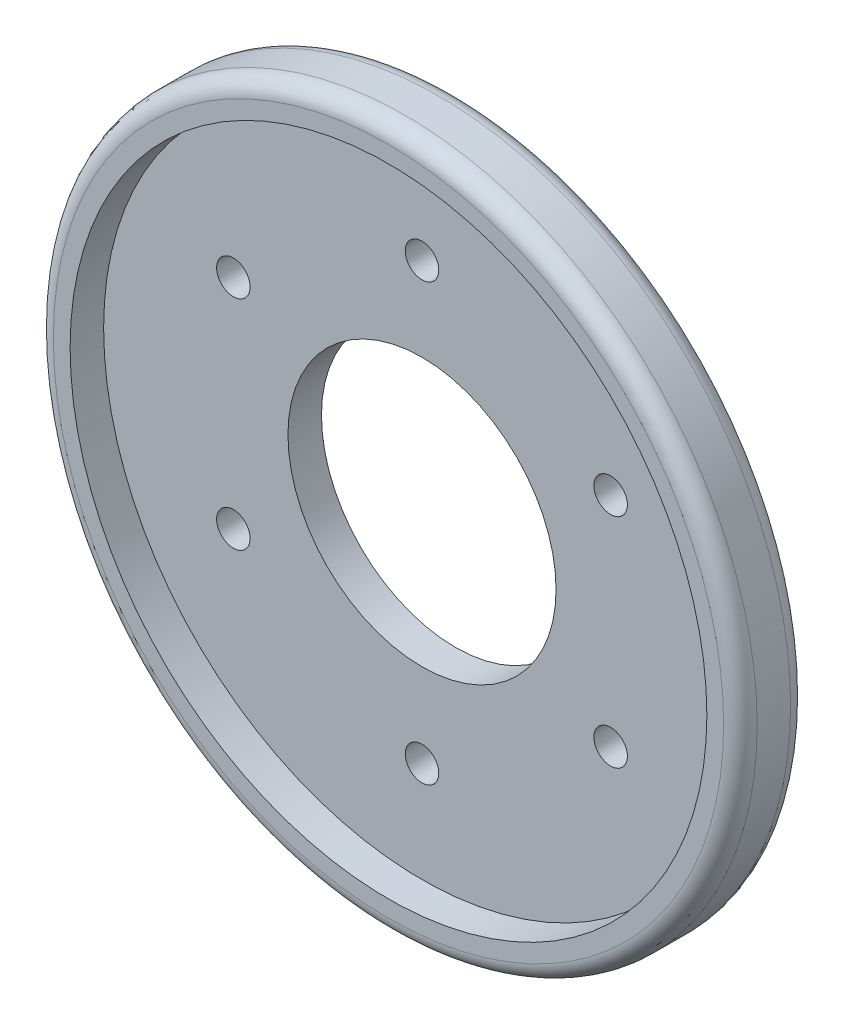
SolidWorks part; units mm, degrees
note: The reader was unsure of these and kept them because the rebuilt part matched: shared geometry of "Эскиз1<5>".
ref_plane "Спереди" through (0, 0, 0) normal (0, 0, 1) x (1, 0, 0)
ref_plane "Сверху" through (0, 0, 0) normal (0, 1, 0) x (1, 0, 0)
ref_plane "Справа" through (0, 0, 0) normal (1, 0, 0) x (0, 0, -1)
other "Configuration Table"
sketch "Эскиз1" plane through (0, 0, 0) normal (0, 0, 1) x (1, 0, 0)
  line L7 (0, 19) -> (0, 21)
  line L8 (0, -21) -> (0, -19)
  circle A0 centre (0, 0) radius 19
  circle A2 centre (0, 0) radius 8
  circle A11 centre (0, 0) radius 21
  point P11 (39.3976, -24.5909)
  dimension "D1" = 38
  dimension "D3" = 16
  dimension "D5" = 21
extrude "Бобышка-Вытянуть1" add sketch "Эскиз1" along normal blind 2
extrude "Бобышка-Вытянуть3" add sketch "Эскиз1<5>" along normal blind 4 contours L7 A11 L8 A0 | L8 A11 L7 A0
sketch "Эскиз1<5>" plane through (0, 0, 0) normal (0, 0, 1) x (1, 0, 0) same geometry as "Эскиз1"
fillet "Скругление1" radius 1 2 edges at (21, 0, 0) (21, 0, 4)
sketch "Эскиз3" plane through (0, 0, 2) normal (0, 0, 1) x (1, 0, 0)
  line L0 (0, 0) -> (0, 12.9985) construction
  line L1 (-11.2571, 6.4993) -> (0, 0) construction
  line L2 (0, 0) -> (11.2571, 6.4993) construction
  circle A6 centre (11.2571, 6.4993) radius 1
  circle A7 centre (11.2571, -6.4993) radius 1
  circle A8 centre (0, -12.9985) radius 1
  circle A9 centre (-11.2571, -6.4993) radius 1
  circle A10 centre (0, 12.9985) radius 1
  circle A11 centre (-11.2571, 6.4993) radius 1
  circle A12 centre (0, 0) radius 12.9985 construction
  point P5 (0, 0)
  point P7 (0, 0)
  dimension "D1" = 2
  dimension "D2" = 25.9971
  dimension "D3" = 60
extrude "Вырез-Вытянуть2" cut sketch "Эскиз3" against normal through all
